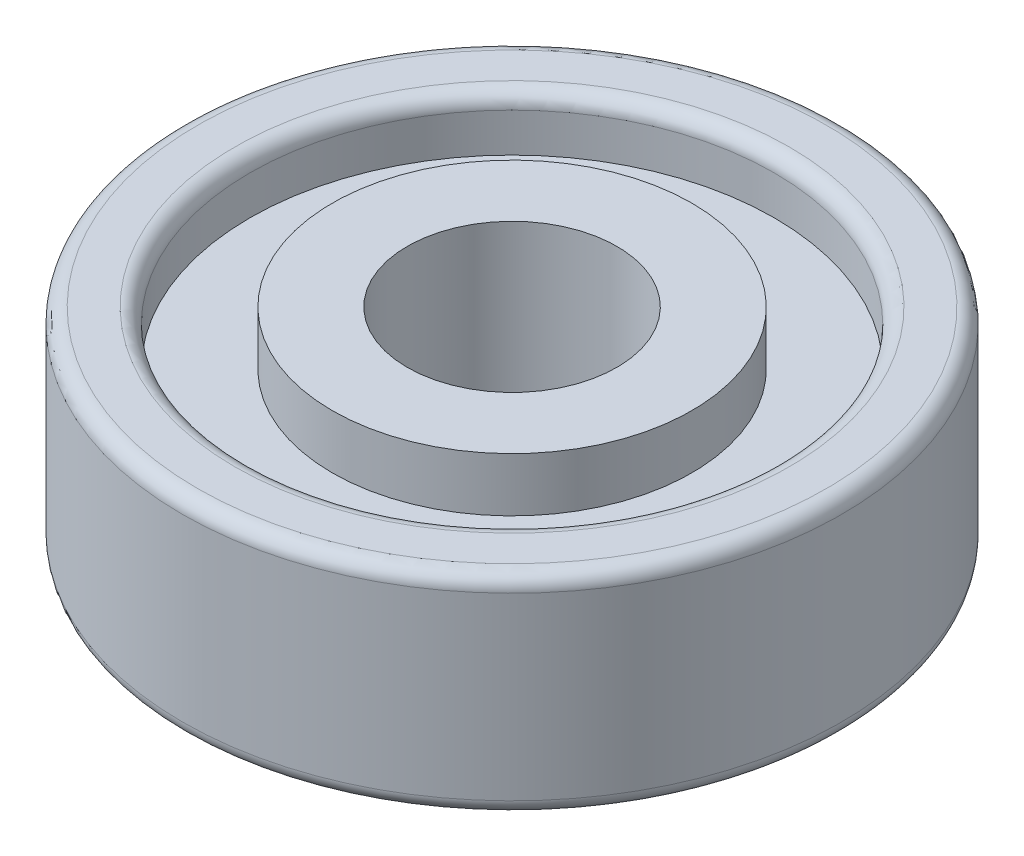
SolidWorks part; units mm, degrees
material "Plain Carbon Steel"
ref_plane "Front Plane" through (0, 0, 0) normal (0, 0, 1) x (1, 0, 0)
ref_plane "Top Plane" through (0, 0, 0) normal (0, 1, 0) x (1, 0, 0)
ref_plane "Right Plane" through (0, 0, 0) normal (1, 0, 0) x (0, 0, -1)
sketch "Sketch1" plane through (0, 0, 0) normal (0, 1, 0) x (1, 0, 0)
  circle A0 centre (0, 0) radius 11
  dimension "D1" = 22
extrude "Boss-Extrude1" add sketch "Sketch1" along normal mid plane 7
sketch "Sketch2" plane through (0, 3.5, 0) normal (0, 1, 0) x (1, 0, 0)
  circle A0 centre (0, 0) radius 8.75
  circle A1 centre (0, 0) radius 3.5
  circle A2 centre (0, 0) radius 6
  dimension "D1" = 7
  dimension "D2" = 17.5
  dimension "D3" = 2.5
extrude "Cut-Extrude1" cut sketch "Sketch2" against normal through all contours A1 region at (0, 3.5, 0)
extrude "Cut-Extrude2" cut sketch "Sketch2<6>" against normal blind 1.8 contours A0 | A2
sketch "Sketch2<6>" plane through (0, 3.5, 0) normal (0, 1, 0) x (1, 0, 0) same geometry as "Sketch2"
mirror "Mirror1" about plane through (0, 0, 0) normal (0, 1, 0) of "Cut-Extrude2"
fillet "Fillet1" radius 0.5 4 edges at (0, 3.5, 11) (0, -3.5, 11) (0, -3.5, 8.75) (0, 3.5, 8.75)
